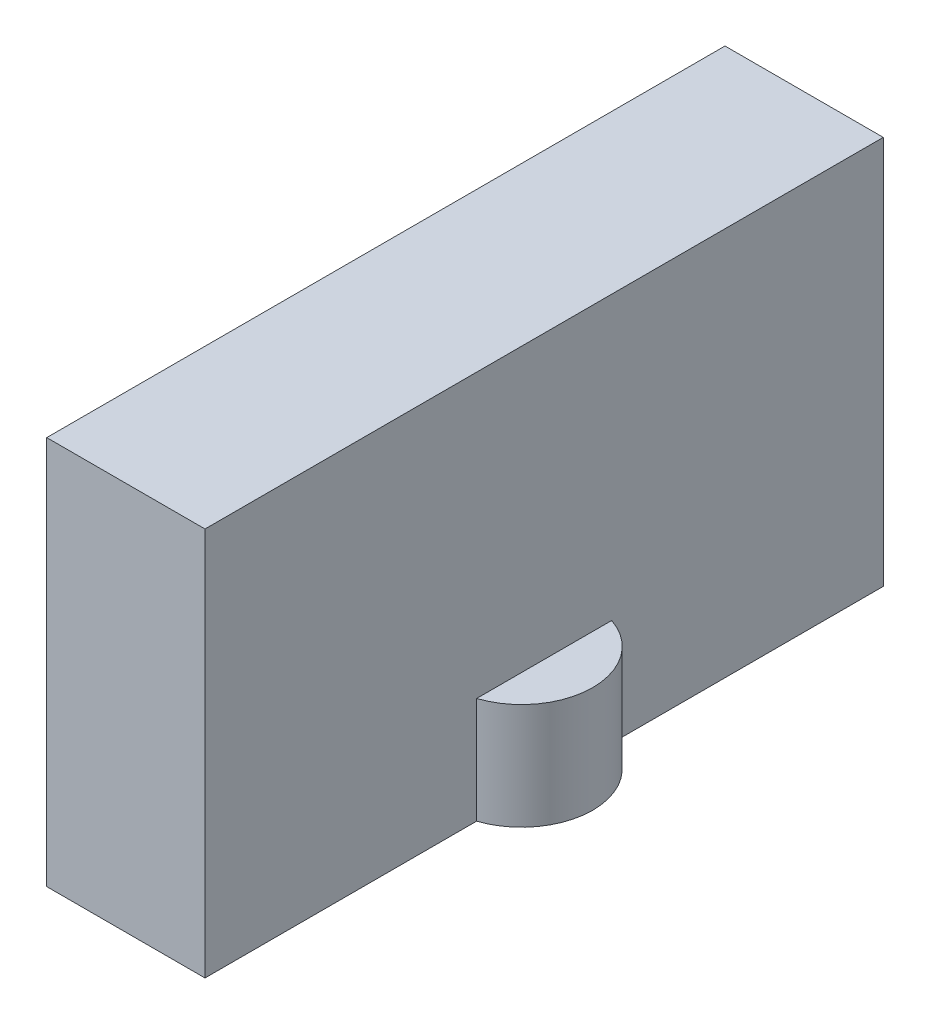
SolidWorks part; units mm, degrees
ref_plane "Front Plane" through (0, 0, 0) normal (0, 0, 1) x (1, 0, 0)
ref_plane "Top Plane" through (0, 0, 0) normal (0, 1, 0) x (1, 0, 0)
ref_plane "Right Plane" through (0, 0, 0) normal (1, 0, 0) x (0, 0, -1)
sketch "Sketch1" plane through (0, 0, 0) normal (0, 1, 0) x (1, 0, 0)
  circle A0 centre (0, 0) radius 31.5
  dimension "D1" = 63
extrude "Boss-Extrude1" add sketch "Sketch1" along normal blind 170
sketch "Sketch2" plane through (0, 170, 0) normal (0, 1, 0) x (1, 0, 0)
  line L0 (10, -150) -> (10, 150)
  line L1 (-60, 150) -> (-60, -150)
  line L2 (-60, -150) -> (10, -150)
  line L3 (-60, 150) -> (10, 150)
  circle A0 centre (0, 0) radius 31.5 construction
  circle M5 centre (0, 0) radius 31.5
  dimension "D2" = 150
  dimension "D3" = 10
  dimension "D1" = 300
  dimension "D4" = 60
extrude "Boss-Extrude2" add sketch "Sketch2" against normal blind 130 and the other way blind 125 contours L3 L1 L0 M5 | L1 L0 M5 | L1 L2 L0 M5 region at (-25, 170, 146.9194) region at (-8.1584, 170, 0)
sketch "Sketch3" plane through (10, 0, 0) normal (1, 0, 0) x (0, 0, -1)
extrude "Boss-Extrude3" add sketch "Sketch2<2>" along normal blind 10
sketch "Sketch2<2>" plane through (0, 170, 0) normal (0, 1, 0) x (1, 0, 0) same geometry as "Sketch2"
sketch "Sketch4" plane through (0, 0, 0) normal (0, -1, 0) x (1, 0, 0)
  line L1 (-157.8447, 216.8943) -> (157.8447, 216.8943)
  line L2 (-157.8447, 216.8943) -> (-157.8447, -216.8943)
  line L3 (-157.8447, -216.8943) -> (157.8447, -216.8943)
  line L4 (157.8447, 216.8943) -> (157.8447, -216.8943)
  line L5 (-157.8447, 216.8943) -> (157.8447, -216.8943) construction
  line L6 (-157.8447, -216.8943) -> (157.8447, 216.8943) construction
  point P0 (0, 0)
extrude "Cut-Extrude2" cut sketch "Sketch4" against normal blind 123 contours L3 L4 L1 L2
ref_point "Point1"
